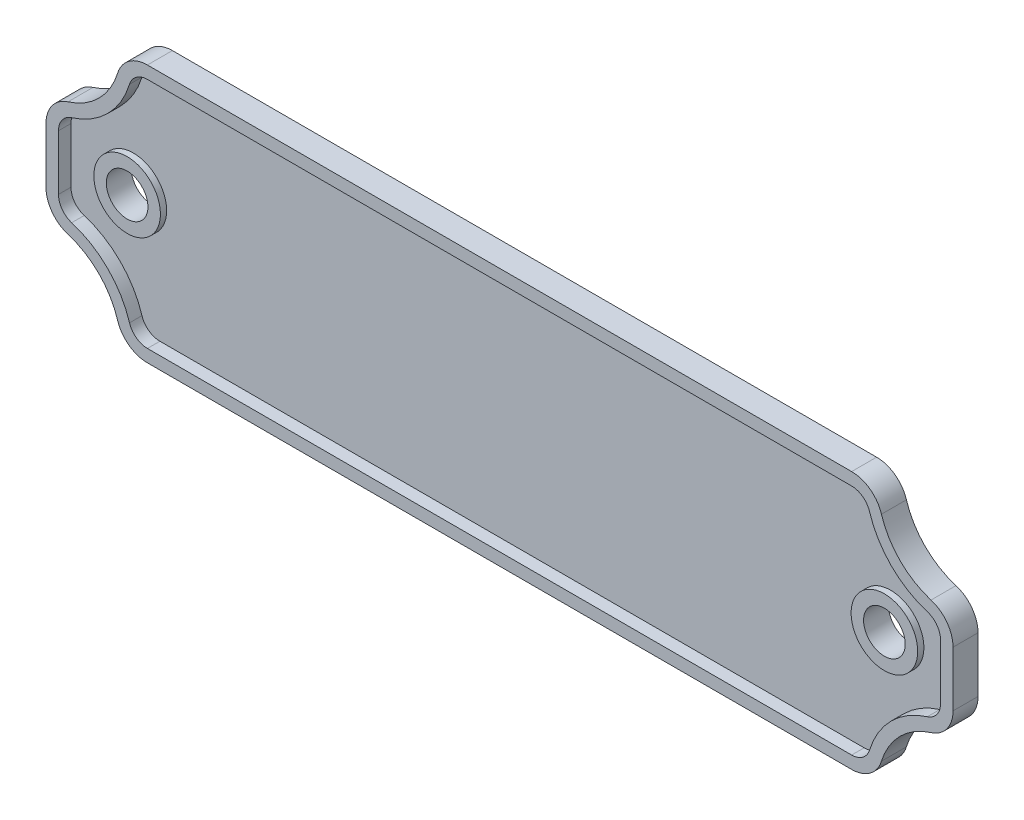
SolidWorks part; units mm, degrees
ref_plane "Front Plane" through (0, 0, 0) normal (0, 0, 1) x (1, 0, 0)
ref_plane "Top Plane" through (0, 0, 0) normal (0, 1, 0) x (1, 0, 0)
ref_plane "Right Plane" through (0, 0, 0) normal (1, 0, 0) x (0, 0, -1)
sketch "Sketch1" plane through (0, 0, 0) normal (0, 0, 1) x (1, 0, 0)
  line L0 (-54.5, 0) -> (54.5, 0) construction
  line L1 (29.975, 0) -> (-29.975, 0) construction
  line L2 (54.5, -3.3139) -> (54.5, 3.3139)
  line L3 (42.3139, 15.5) -> (-42.3139, 15.5)
  line L4 (0, -8.525) -> (0, 8.525) construction
  line L5 (0, 15.5) -> (0, -15.5) construction
  line L6 (-54.5, -3.3139) -> (-54.5, 3.3139)
  line L7 (42.3139, -15.5) -> (-42.3139, -15.5)
  line L8 (53, -3.3139) -> (53, 3.3139)
  line L9 (42.3139, 14) -> (-42.3139, 14)
  line L10 (-53, -3.3139) -> (-53, 3.3139)
  line L11 (42.3139, -14) -> (-42.3139, -14)
  arc A0 (51.8529, 6.8981) -> (45.8981, 12.8529) centre (54.5, 15.5) cw
  arc A1 (54.5, 3.3139) -> (51.8529, 6.8981) centre (50.75, 3.3139) ccw
  arc A2 (45.8981, 12.8529) -> (42.3139, 15.5) centre (42.3139, 11.75) ccw
  arc A3 (-45.8981, 12.8529) -> (-42.3139, 15.5) centre (-42.3139, 11.75) cw
  arc A4 (-54.5, 3.3139) -> (-51.8529, 6.8981) centre (-50.75, 3.3139) cw
  arc A5 (-51.8529, 6.8981) -> (-45.8981, 12.8529) centre (-54.5, 15.5) ccw
  arc A6 (-51.8529, -6.8981) -> (-45.8981, -12.8529) centre (-54.5, -15.5) cw
  arc A7 (-54.5, -3.3139) -> (-51.8529, -6.8981) centre (-50.75, -3.3139) ccw
  arc A8 (-45.8981, -12.8529) -> (-42.3139, -15.5) centre (-42.3139, -11.75) ccw
  arc A9 (45.8981, -12.8529) -> (42.3139, -15.5) centre (42.3139, -11.75) cw
  arc A10 (54.5, -3.3139) -> (51.8529, -6.8981) centre (50.75, -3.3139) cw
  arc A11 (51.8529, -6.8981) -> (45.8981, -12.8529) centre (54.5, -15.5) ccw
  arc A12 (53, 3.3139) -> (51.4118, 5.4644) centre (50.75, 3.3139) ccw
  arc A13 (51.4118, 5.4644) -> (44.4644, 12.4118) centre (54.5, 15.5) cw
  arc A14 (44.4644, 12.4118) -> (42.3139, 14) centre (42.3139, 11.75) ccw
  arc A15 (-44.4644, 12.4118) -> (-42.3139, 14) centre (-42.3139, 11.75) cw
  arc A16 (-51.4118, 5.4644) -> (-44.4644, 12.4118) centre (-54.5, 15.5) ccw
  arc A17 (-53, 3.3139) -> (-51.4118, 5.4644) centre (-50.75, 3.3139) cw
  arc A18 (-53, -3.3139) -> (-51.4118, -5.4644) centre (-50.75, -3.3139) ccw
  arc A19 (-51.4118, -5.4644) -> (-44.4644, -12.4118) centre (-54.5, -15.5) cw
  arc A20 (-44.4644, -12.4118) -> (-42.3139, -14) centre (-42.3139, -11.75) ccw
  arc A21 (44.4644, -12.4118) -> (42.3139, -14) centre (42.3139, -11.75) cw
  arc A22 (51.4118, -5.4644) -> (44.4644, -12.4118) centre (54.5, -15.5) ccw
  arc A23 (53, -3.3139) -> (51.4118, -5.4644) centre (50.75, -3.3139) cw
  circle A24 centre (-45.5, 0) radius 4
  circle A25 centre (-45.5, 0) radius 2.5
  circle A26 centre (45.5, 0) radius 4
  circle A27 centre (45.5, 0) radius 2.5
  point P38 (0, 0)
  dimension "D3" = 9
  dimension "D4" = 3.75
  dimension "D7" = 8
  dimension "D8" = 5
  dimension "D1" = 54.5
  dimension "D2" = 15.5
  dimension "D6" = 9
  dimension "D5" = 1.5
extrude "Boss-Extrude3" add sketch "Sketch1" along normal blind 1.5 contours A11 A10 L2 A1 A0 A2 L3 A3 A5 A4 L6 A7 A6 A8 L7 A9 L8 A23 A22 A21 L11 A20 A19 A18 L10 A17 A16 A15 L9 A14 A13 A12 | A23 L8 A12 A13 A14 L9 A15 A16 A17 L10 A18 A19 A20 L11 A21 A22 A24 A26 | A24 A25 region at (52.8549, -4.8685, 0) region at (0, 0, 0) region at (-49.3869, 0, 0)
extrude "Boss-Extrude4" add sketch "Sketch1<3>" along normal blind 3 contours A11 A10 L2 A1 A0 A2 L3 A3 A5 A4 L6 A7 A6 A8 L7 A9 L8 A23 A22 A21 L11 A20 A19 A18 L10 A17 A16 A15 L9 A14 A13 A12 region at (52.8549, -4.8685, 0)
sketch "Sketch1<3>" plane through (0, 0, 0) normal (0, 0, 1) x (1, 0, 0) same geometry as "Sketch1"
extrude "Boss-Extrude5" add sketch "Sketch1<6>" along normal blind 2.25 and the other way blind 0.75 contours A24 A25 region at (-49.3869, 0, 0)
sketch "Sketch1<6>" plane through (0, 0, 0) normal (0, 0, 1) x (1, 0, 0) same geometry as "Sketch1"
mirror "Mirror1" about plane through (0, 0, 0) normal (1, 0, 0) of "Boss-Extrude5"
